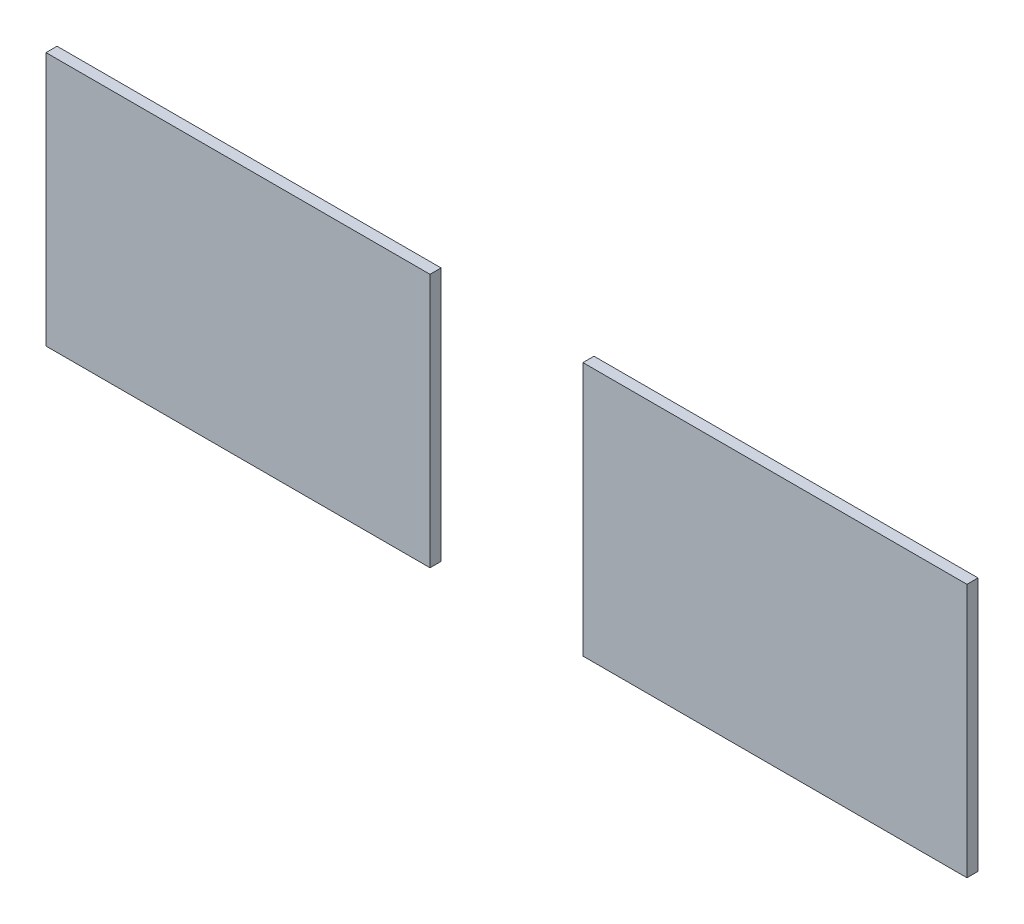
SolidWorks part; units mm, degrees
material "Pine"
ref_plane "Front Plane" through (0, 0, 0) normal (0, 0, 1) x (1, 0, 0)
ref_plane "Top Plane" through (0, 0, 0) normal (0, 1, 0) x (1, 0, 0)
ref_plane "Right Plane" through (0, 0, 0) normal (1, 0, 0) x (0, 0, -1)
sketch "Sketch1" plane through (0, 0, 0) normal (0, 0, 1) x (1, 0, 0)
  line L6 (0, 0) -> (1000, 0)
  line L10 (0, 0) -> (0, 276)
  line L11 (0, 276) -> (1000, 276)
  line L12 (1000, 0) -> (1000, 276)
  dimension "D3" = 276
  dimension "D1" = 1000
extrude "Boss-Extrude1" add sketch "Sketch1" along normal blind 12 contours L10 L11 L12 L6
sketch "Sketch2" plane through (0, 0, 12) normal (0, 0, 1) x (1, 0, 0)
  line L0 (500, 276) -> (500, 0) construction
  line L1 (0, 276) -> (1000, 276) construction
  line L2 (0, 0) -> (1000, 0) construction
  line L4 (417, 276) -> (583, 276)
  line L5 (417, 276) -> (417, 0)
  line L6 (417, 0) -> (583, 0)
  line L7 (583, 276) -> (583, 0)
  line L8 (417, 276) -> (583, 0) construction
  line L9 (417, 0) -> (583, 276) construction
  point P6 (500, 138)
  dimension "D1" = 166
extrude "Cut-Extrude1" cut sketch "Sketch2" against normal up to surface (12 mm away) up to face at (500, 138, 0)
equation "\"LENGTH\" = 1000mm"
equation "\"D1@Sketch1\"=\"LENGTH\""
equation "\"PLY\"= 12mm"
equation "\"D1@Boss-Extrude1\"=\"PLY\""
equation "\"CENTER_BRACE_LENGTH\" = 393mm"
equation "\"D1@Sketch2\"=\"LENGTH\" - \"CENTER_BRACE_LENGTH\" * 2 - \"PLY\" * 4"
equation "\"PANEL_WIDTH\"= \"LENGTH\" - \"CENTER_BRACE_LENGTH\" * 2 - \"PLY\" * 4"
